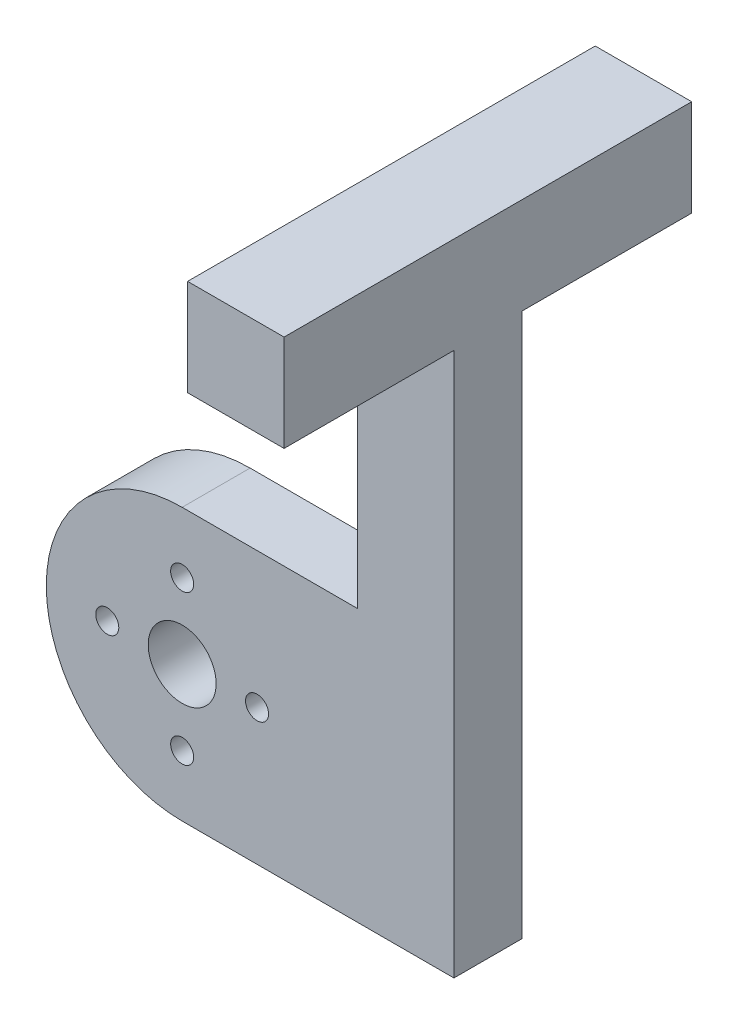
SolidWorks part; units mm, degrees
ref_plane "Front Plane" through (0, 0, 0) normal (0, 0, 1) x (1, 0, 0)
ref_plane "Top Plane" through (0, 0, 0) normal (0, 1, 0) x (1, 0, 0)
ref_plane "Right Plane" through (0, 0, 0) normal (1, 0, 0) x (0, 0, -1)
sketch "Sketch2" plane through (0, 0, 0) normal (0, 0, 1) x (1, 0, 0)
  line L0 (16.383, 47.117) -> (25.4, 47.117)
  line L1 (16.383, 47.117) -> (16.383, 12.7)
  line L2 (16.383, 12.7) -> (0, 12.7)
  line L3 (25.4, 47.117) -> (25.4, -12.7)
  line L4 (25.4, -12.7) -> (0, -12.7)
  circle A0 centre (0, 0) radius 12.7
  circle A1 centre (7, 0) radius 1.077
  circle A2 centre (0, -7) radius 1.077
  circle A3 centre (-7, 0) radius 1.077
  circle A4 centre (0, 7) radius 1.077
  point P14 (0, 0)
  dimension "D1" = 25.4
  dimension "D3" = 2.154
  dimension "D2" = 7
  dimension "D5" = 47.117
  dimension "D6" = 16.383
  dimension "D7" = 25.4
  dimension "D8" = 9.017
  dimension "D4" = 4
extrude "Boss-Extrude1" add sketch "Sketch2" along normal mid plane 6.35 contours A0 L4 L3 L0 L1 L2 | A0 A4 A3 A2 A1 region at (18.9582, 13.2191, 0) region at (0, 0, 0)
sketch "Sketch3" plane through (0, 0, 0) normal (0, 0, -1) x (-1, 0, 0)
  line L0 (-16.383, 47.117) -> (-16.383, 12.7) construction
  line L1 (-25.4, 47.117) -> (-16.383, 47.117)
  line L2 (-25.4, 47.117) -> (-25.4, 38.1)
  line L3 (-25.4, 38.1) -> (-16.383, 38.1)
  line L4 (-16.383, 47.117) -> (-16.383, 38.1)
extrude "Boss-Extrude2" add sketch "Sketch3" along normal mid plane 38.1
sketch "Sketch4" plane through (0, 0, 3.175) normal (0, 0, 1) x (1, 0, 0)
  circle A0 centre (0, 0) radius 3.175
  dimension "D1" = 6.35
extrude "Cut-Extrude1" cut sketch "Sketch4" against normal through all
equation "\"D2@Sketch2\"=7mm"
equation "\"tightTol\" = 0.005in"
equation "\"normTol\" = 0.01in"
equation "\"looseTol\" = 0.02in"
equation "\"D3@Sketch2\"=1.9mm+\"normTol\""
equation "\"D6@Sketch2\"=0.625+\"looseTol\""
equation "\"D5@Sketch2\"=1.875-\"looseTol\""
